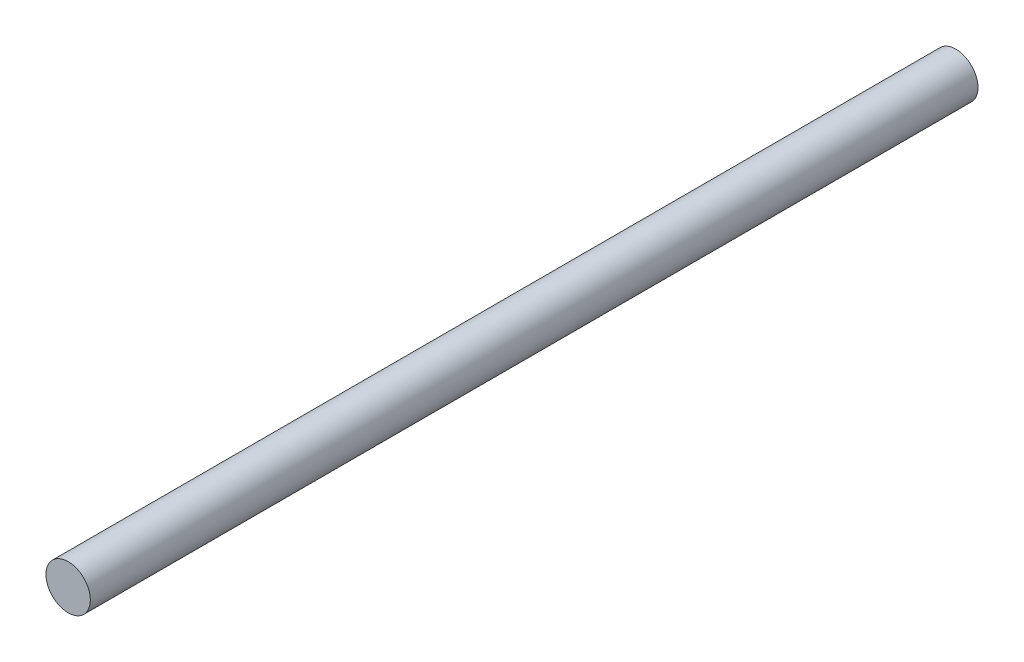
SolidWorks part; units mm, degrees
ref_plane "Front Plane" through (0, 0, 0) normal (0, 0, 1) x (1, 0, 0)
ref_plane "Top Plane" through (0, 0, 0) normal (0, 1, 0) x (1, 0, 0)
ref_plane "Right Plane" through (0, 0, 0) normal (1, 0, 0) x (0, 0, -1)
sketch "Sketch1" plane through (0, 0, 0) normal (0, 0, 1) x (1, 0, 0)
  circle A0 centre (0, 0) radius 6.35
  dimension "D1" = 12.7
extrude "Boss-Extrude1" add sketch "Sketch1" along normal blind 127 and the other way blind 127
